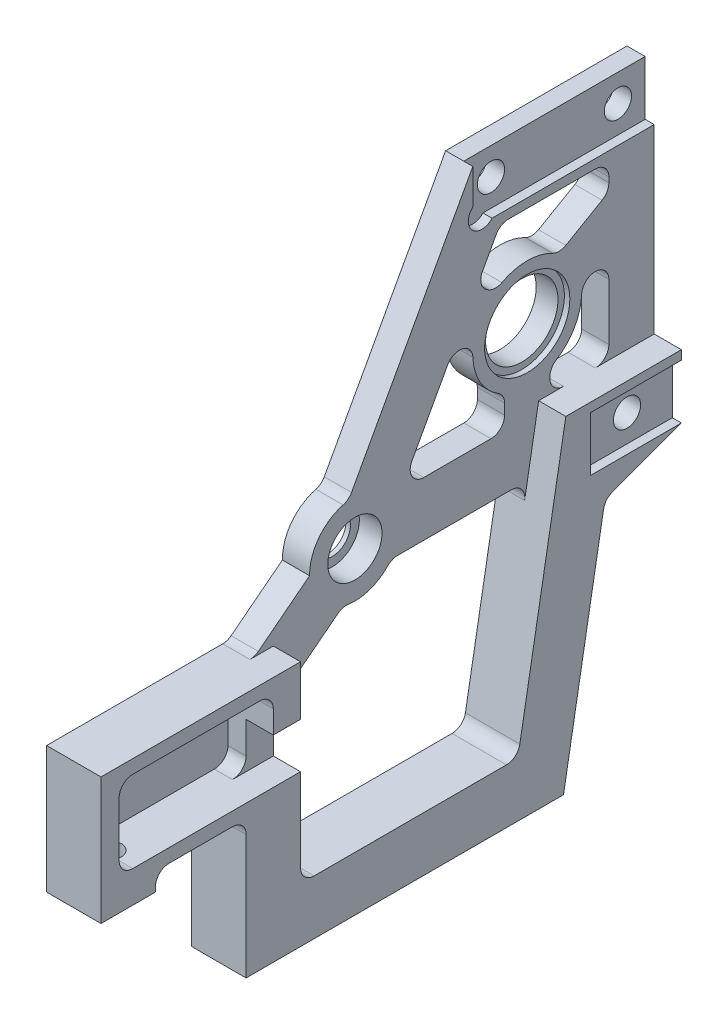
SolidWorks part; units mm, degrees
material "1060 Alloy"
ref_plane "Front Plane" through (0, 0, 0) normal (0, 0, 1) x (1, 0, 0)
ref_plane "Top Plane" through (0, 0, 0) normal (0, 1, 0) x (1, 0, 0)
ref_plane "Right Plane" through (0, 0, 0) normal (1, 0, 0) x (0, 0, -1)
sketch "Sketch1" plane through (0, 0, 0) normal (1, 0, 0) x (0, 0, -1)
  line L0 (51, 0) -> (55.5726, 25.9327)
  line L1 (16, 0) -> (51, 0)
  line L2 (0, 13.2) -> (0, 27.2)
  line L3 (44, 62) -> (64, 62)
  line L4 (64, 29) -> (64, 62)
  line L5 (55.5726, 25.9327) -> (64, 29)
  line L6 (16, 0) -> (16, 15.2)
  line L7 (16, 15.2) -> (6, 15.2)
  line L8 (0, 27.2) -> (19.9415, 27.2)
  line L9 (44, 62) -> (30.2889, 36.9492)
  line L10 (44, 62) -> (44, 56) construction
  line L11 (44, 56) -> (64, 56) construction
  line L12 (64, 29) -> (54, 29) construction
  line L13 (54, 29) -> (54, 35) construction
  line L14 (54, 35) -> (64, 35) construction
  line L15 (31, 32) -> (44, 55.7516) construction
  line L16 (41.9513, 45.7601) -> (36.062, 35)
  line L17 (31, 32) -> (59, 32) construction
  line L18 (50, 44) -> (58.0527, 48.6492) construction
  line L19 (41.9513, 45.7601) -> (44.0264, 44.5621)
  line L20 (47.0086, 55) -> (44.3526, 50.1473)
  line L21 (44.3526, 50.1473) -> (46.5264, 48.8922)
  line L22 (50, 44) -> (50, 36.0123) construction
  line L23 (59, 52.0829) -> (59, 55)
  line L24 (59, 55) -> (47.0086, 55)
  line L25 (31, 32) -> (19.9305, 23.391) construction
  line L26 (59, 46.3094) -> (59, 36)
  line L27 (59, 36) -> (52.5, 36)
  line L28 (52.5, 36) -> (52.5, 38.5456)
  line L29 (47.5, 35) -> (36.062, 35)
  line L30 (35, 29) -> (50.0209, 29)
  line L31 (22, 21.2) -> (29.6843, 27.1762)
  line L32 (50.0209, 29) -> (45.9654, 6)
  line L33 (45.9654, 6) -> (22, 6)
  line L34 (22, 6) -> (22, 21.2)
  line L35 (6, 15.2) -> (6, 13.2)
  line L36 (26.0008, 31.9125) -> (19.9415, 27.2)
  line L37 (6, 13.2) -> (0, 13.2)
  line L38 (47.5, 35) -> (47.5, 38.5456)
  line L40 (59, 52.0829) -> (53.4736, 48.8922)
  line L41 (59, 46.3094) -> (55.9736, 44.5621)
  line L42 (50, 44) -> (37.9544, 50.9545) construction
  circle A0 centre (59, 32) radius 1.5
  circle A1 centre (50, 44) radius 3.99
  circle A2 centre (61, 59) radius 1.5
  circle A3 centre (47, 59) radius 1.5
  circle A4 centre (31, 32) radius 2
  circle A5 centre (31, 32) radius 5 construction
  arc A6 (46.5264, 48.8922) -> (53.4736, 48.8922) centre (50, 44) cw
  arc A7 (52.5, 38.5456) -> (55.9736, 44.5621) centre (50, 44) ccw
  arc A8 (29.6843, 27.1762) -> (35, 29) centre (31, 32) ccw
  arc A9 (30.2889, 36.9492) -> (26.0008, 31.9125) centre (31, 32) ccw
  arc A11 (44.0264, 44.5621) -> (47.5, 38.5456) centre (50, 44) ccw
  dimension "D1" = 7.98
  dimension "D2" = 16
  dimension "D4" = 3
  dimension "D14" = 4
  dimension "D24" = 10
  dimension "D27" = 6
  dimension "D3" = 15.2
  dimension "D5" = 44
  dimension "D6" = 50
  dimension "D7" = 64
  dimension "D8" = 62
  dimension "D9" = 3
  dimension "D10" = 14
  dimension "D11" = 3
  dimension "D12" = 3
  dimension "D13" = 5
  dimension "D15" = 12
  dimension "D16" = 32
  dimension "D17" = 31
  dimension "D18" = 32
  dimension "D19" = 6
  dimension "D20" = 20
  dimension "D21" = 10
  dimension "D22" = 6
  dimension "D23" = 51
  dimension "D25" = 6
  dimension "D26" = 3
  dimension "D28" = 5
  dimension "D29" = 2.5
  dimension "D30" = 5
  dimension "D31" = 6
  dimension "D32" = 3
  dimension "D33" = 1
  dimension "D34" = 120
  dimension "D35" = 1
  dimension "D36" = 6
  dimension "D37" = 6
  dimension "D38" = 20
  dimension "D39" = 100
  dimension "D40" = 6
  dimension "D41" = 6
  dimension "D42" = 120
  dimension "D43" = 2.5
  dimension "D44" = 2.5
  dimension "D45" = 2.5
  dimension "D46" = 2.5
  dimension "D47" = 3
  dimension "D48" = 3
  dimension "D49" = 2
  dimension "D50" = 6
extrude "Boss-Extrude1" add sketch "Sketch1" along normal blind 6
hole_wizard "Tap Drill for M3 Tap1" positions "Sketch5" profile "Sketch4" hole size "M3" standard "ISO"
sketch "Sketch5" plane through (0, 0, 0) normal (0, -1, 0) x (-1, 0, 0)
  line L0 (0, 16) -> (0, 51) construction
  line L2 (-6, 51) -> (0, 51) construction
  line L4 (-6, 16) -> (0, 16) construction
  point P0 (-3, 48)
  point P2 (-3, 19)
  dimension "D1" = 3
  dimension "D2" = 3
  dimension "D3" = 3
sketch "Sketch4" plane through (3, 0, -48) normal (1, 0, 0) x (0, 0, -1)
  line L0 (0, 0) -> (0, 9.7511)
  line L1 (0, 9.7511) -> (1.25, 9)
  line L2 (1.25, 9) -> (1.25, 0)
  line L5 (1.25, 0) -> (0, 0)
  line L10 (0, 9.7511) -> (-1.25, 9) construction
  line L11 (0, -6.35) -> (0, 107.95) construction
  dimension "Hole Dia." = 2.5
  dimension "Hole Depth" = 9
  dimension "Drill Angle" = 118
sketch "Sketch13" plane through (6, 0, 0) normal (1, 0, 0) x (0, 0, -1)
  line L0 (64, 29) -> (64, 62) construction
  line L1 (51.2552, 36) -> (64, 36)
  line L2 (64, 62) -> (44, 62) construction
  line L3 (64, 62) -> (44, 62)
  line L4 (64, 36) -> (64, 62)
  line L5 (30.2889, 36.9492) -> (19.9415, 36.9492)
  line L6 (22, 21.2) -> (22, 6) construction
  line L10 (29.6843, 27.1762) -> (22, 21.2) construction
  line L11 (44, 62) -> (30.2889, 36.9492)
  line L12 (22, 21.2) -> (50.0209, 29)
  line L13 (44, 62) -> (30.2889, 36.9492) construction
  line L14 (50.0209, 29) -> (51.2552, 36)
  line L20 (22, 21.2) -> (22, 27.2)
  line L21 (22, 27.2) -> (19.9415, 27.2)
  line L22 (19.9415, 27.2) -> (0, 27.2) construction
  line L23 (19.9415, 27.2) -> (19.9415, 36.9492)
  line L24 (45.9654, 6) -> (50.0209, 29) construction
  arc A2 (30.2889, 36.9492) -> (26.0008, 31.9125) centre (31, 32) ccw construction
  dimension "D3" = 26
extrude "Cut-Extrude4" cut sketch "Sketch13" against normal blind 3
sketch "Sketch14" plane through (3, 0, 0) normal (1, 0, 0) x (0, 0, -1)
  line L1 (64, 62) -> (44, 62)
  line L2 (64, 62) -> (64, 56)
  line L3 (64, 56) -> (44, 56)
  line L4 (44, 62) -> (44, 56)
  dimension "D1" = 6
extrude "Cut-Extrude5" cut sketch "Sketch14" against normal blind 1
sketch "Sketch15" plane through (6, 0, 0) normal (1, 0, 0) x (0, 0, -1)
  line L1 (64, 29) -> (54, 29)
  line L2 (64, 29) -> (64, 35)
  line L3 (64, 35) -> (54, 35)
  line L4 (54, 29) -> (54, 35)
  dimension "D1" = 10
  dimension "D2" = 6
extrude "Cut-Extrude6" cut sketch "Sketch15" against normal blind 1
sketch "Sketch16" plane through (3, 0, 0) normal (1, 0, 0) x (0, 0, -1)
  circle A0 centre (31, 32) radius 2.99
  dimension "D1" = 5.98
extrude "Cut-Extrude7" cut sketch "Sketch16" against normal blind 2.5
sketch "Sketch17" plane through (6, 0, 0) normal (1, 0, 0) x (0, 0, -1)
  line L0 (0, 27.2) -> (0, 13.2) construction
  line L1 (2, 25.7) -> (19, 25.7)
  line L2 (2, 25.7) -> (2, 16.7)
  line L3 (2, 16.7) -> (19, 16.7)
  line L4 (19, 25.7) -> (19, 16.7)
  line L5 (22, 27.2) -> (0, 27.2) construction
  line L6 (6, 15.2) -> (16, 15.2) construction
  line L7 (22, 27.2) -> (22, 6) construction
  dimension "D1" = 2
  dimension "D2" = 1.5
  dimension "D3" = 1.5
  dimension "D4" = 3
extrude "Cut-Extrude8" cut sketch "Sketch17" against normal offset from surface (5 mm away) 1 up to face at (0, 40.1727, -55.9866)
fillet "Fillet1" radius 1.5 4 edges at (3.5, 25.7, -2) (3.5, 16.7, -2) (3.5, 16.7, -19) (3.5, 25.7, -19)
sketch "Sketch18" plane through (1, 0, 0) normal (1, 0, 0) x (0, 0, -1)
  line L0 (5, 23.7) -> (16.5, 23.7) construction
  line L1 (5, 25.2) -> (16.5, 25.2)
  line L2 (5, 22.2) -> (16.5, 22.2)
  line L3 (17.5, 25.7) -> (3.5, 25.7) construction
  line L4 (2, 24.2) -> (2, 18.2) construction
  line L5 (19, 18.2) -> (19, 24.2) construction
  arc A0 (5, 25.2) -> (5, 22.2) centre (5, 23.7) ccw
  arc A1 (16.5, 22.2) -> (16.5, 25.2) centre (16.5, 23.7) ccw
  point P2 (10.75, 23.7)
  dimension "D1" = 3
  dimension "D2" = 2
  dimension "D3" = 3
  dimension "D4" = 2.5
extrude "Cut-Extrude9" cut sketch "Sketch18" against normal up to next
sketch "Sketch19" plane through (6, 0, 0) normal (1, 0, 0) x (0, 0, -1)
  line L0 (22, 27.2) -> (22, 6) construction
  line L1 (22, 21.7) -> (17.5, 21.7)
  line L2 (22, 21.7) -> (22, 16.7)
  line L3 (22, 16.7) -> (17.5, 16.7)
  line L4 (17.5, 21.7) -> (17.5, 16.7)
  dimension "D1" = 5
extrude "Cut-Extrude10" cut sketch "Sketch19" against normal blind 3
sketch "Sketch20" plane through (3, 0, 0) normal (1, 0, 0) x (0, 0, -1)
  circle A0 centre (50, 44) radius 4.7
  dimension "D1" = 9.4
extrude "Cut-Extrude11" cut sketch "Sketch20" against normal blind 0.6
fillet "Fillet2" radius 1.5 16 edges at (1.5, 55, -47.0086) (1.5, 50.1473, -44.3526) (1.5, 48.8922, -46.5264) (1.5, 48.8922, -53.4736) (1.5, 55, -59) (1.5, 52.0829, -59) (1.5, 44.5621, -55.9736) (1.5, 46.3094, -59) (1.5, 38.5456, -52.5) (1.5, 36, -52.5) (1.5, 36, -59) (1.5, 35, -36.062) (1.5, 35, -47.5) (1.5, 38.5456, -47.5) (1.5, 45.7601, -41.9513) (1.5, 44.5621, -44.0264)
fillet "Fillet3" radius 1.5 11 edges at (1.5, 29, -50.0209) (3, 6, -45.9654) (3, 6, -22) (1.5, 29, -35) (1.5, 27.1762, -29.6843) (1.5, 27.2, -19.9415) (1.5, 36.9492, -30.2889) (3, 15.2, -16) (1.5, 21.2, -22) (3, 15.2, -6) (3, 25.9327, -55.5726)
hole_wizard "Tap Drill for M3 Tap2" positions "Sketch22" profile "Sketch21" hole size "M3" standard "ISO" end condition up to next
sketch "Sketch22" plane through (0, 13.2, 0) normal (0, -1, 0) x (-1, 0, 0)
  line L0 (-6, 0) -> (0, 0) construction
  line L1 (0, 7.5) -> (0, 14.5) construction
  point P0 (-3, 4)
  dimension "D1" = 4
  dimension "D2" = 3
sketch "Sketch21" plane through (3, 13.2, -4) normal (1, 0, 0) x (0, 0, -1)
  line L0 (0, 0) -> (0, 3.5)
  line L1 (0, 3.5) -> (1.25, 3.5)
  line L2 (1.25, 3.5) -> (1.25, 0)
  line L5 (1.25, 0) -> (0, 0)
  line L11 (0, -6.35) -> (0, 107.95) construction
  dimension "Thru Hole Dia." = 2.5
  dimension "Thru Hole Depth" = 3.5
sketch "Sketch23" plane through (3, 0, 0) normal (1, 0, 0) x (0, 0, -1)
  line L0 (44, 56) -> (64, 56) construction
  line L1 (44, 62) -> (44, 56) construction
  circle A0 centre (45, 57) radius 1.5
  dimension "D1" = 3
  dimension "D2" = 1
  dimension "D3" = 1
extrude "Cut-Extrude12" cut sketch "Sketch23" against normal up to surface (1 mm away) up to face at (2, 59, -59.5)
